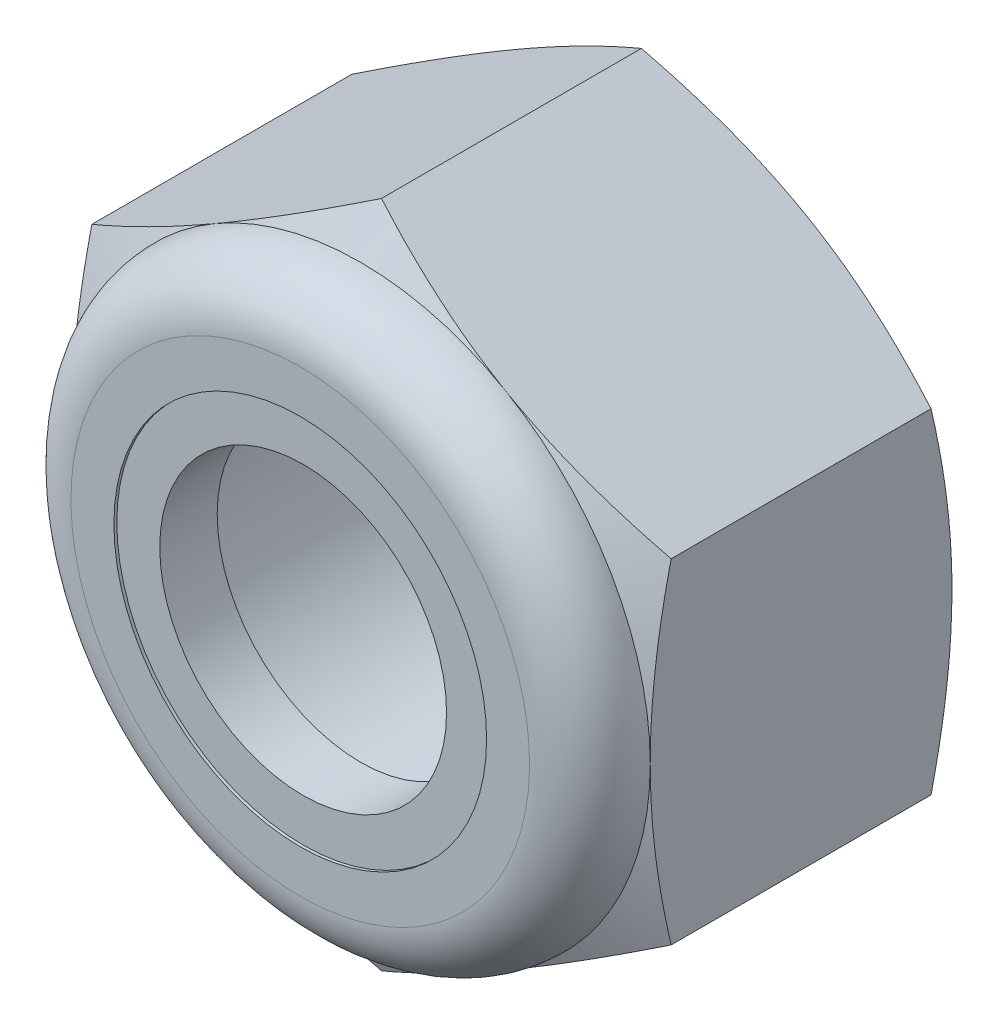
SolidWorks part; units mm, degrees
material "Alloy Steel"
ref_plane "Front Plane" through (0, 0, 0) normal (0, 0, 1) x (1, 0, 0)
ref_plane "Top Plane" through (0, 0, 0) normal (0, 1, 0) x (1, 0, 0)
ref_plane "Right Plane" through (0, 0, 0) normal (1, 0, 0) x (0, 0, -1)
sketch "Sketch1" plane through (0, 0, 0) normal (0, 0, 1) x (1, 0, 0)
  line L1 (0, 4.6188) -> (-4, 2.3094)
  line L2 (-4, 2.3094) -> (-4, -2.3094)
  line L3 (-4, -2.3094) -> (0, -4.6188)
  line L4 (0, -4.6188) -> (4, -2.3094)
  line L5 (4, -2.3094) -> (4, 2.3094)
  line L6 (4, 2.3094) -> (0, 4.6188)
  circle A0 centre (0, 0) radius 4 construction
  circle A1 centre (0, 0) radius 2.5
  point P10 (0, -2.5)
  point P11 (0, 2.5)
  point P12 (0, 4)
  dimension "Thread Size" = 5
  dimension "Width" = 8
sketch "Sketch2" plane through (0, 0, 0) normal (1, 0, 0) x (0, 0, -1)
  line L0 (2.5, 0) -> (-2.5, 0) construction
  line L1 (-2.5, 2.5) -> (2.5, 2.5) construction
  line L2 (-2.46, -2.5735) -> (-3.77, -2.5735) construction
  line L3 (-3.25, 2.5866) -> (-2.45, 2.5866) construction
  line L4 (-2.45, 2.5866) -> (-2.85, 1.8938) construction
  line L5 (-2.85, 1.8938) -> (-3.25, 2.5866) construction
  line L6 (-3.2, 2.5) -> (-2.5, 2.5) construction
  line L7 (-2.9, 1.9804) -> (-2.8, 1.9804) construction
  line L8 (-2.85, 1.9804) -> (-2.85, 1.8938) construction
  line L9 (-2.85, 2.5) -> (-2.85, 2.5866) construction
  line L10 (-2.475, 2.5433) -> (-3.225, 2.5433)
  line L11 (-3.225, 2.5433) -> (-2.9, 1.9804)
  line L12 (-2.9, 1.9804) -> (-2.8, 1.9804)
  line L13 (-2.8, 1.9804) -> (-2.475, 2.5433)
  line L14 (2.5, 0) -> (3.77, 0)
  line L15 (3.77, 0) -> (3.77, 5.8888)
  line L16 (0, 5.8888) -> (0, 4.6188) construction
  line L17 (0, 4.6188) -> (0, 2.3094) construction
  line L18 (2.5, 4) -> (-1.6667, 4) construction
  line L19 (-2.9, -1.9804) -> (-2.8, -1.9804) construction
  line L20 (2.5, 4) -> (2.5, 0)
  line L21 (2.2114, 4.6188) -> (-1.3781, 4.6188)
  line L22 (2.5, 4) -> (2.2114, 4.6188)
  line L23 (-2.5, 0) -> (-2.5, 3.1667) construction
  line L24 (-1.6667, 4) -> (-1.3781, 4.6188)
  line L25 (3.77, 5.8888) -> (-3.77, 5.8888)
  line L26 (-2.5, 3.1667) -> (-3.77, 3.1667)
  line L27 (-3.77, 3.1667) -> (-3.77, 5.8888)
  line L28 (-2.46, 3.1667) -> (-2.46, 1.9804) construction
  line L29 (-2.46, 2.5735) -> (-3.77, 2.5735)
  line L30 (-3.77, 2.5735) -> (-3.77, 0)
  line L31 (-3.77, 0) -> (-1.6667, 0)
  line L32 (-1.6667, 0) -> (-1.6667, 3.96)
  line L33 (-2.46, 2.5735) -> (-2.46, 3.1667)
  arc A0 (-1.6667, 4) -> (-2.5, 3.1667) centre (-1.6667, 3.1667) ccw
  arc A1 (-1.6667, 3.96) -> (-2.46, 3.1667) centre (-1.6667, 3.1667) ccw
  point P4 (0, 0)
  point P18 (-2.85, 2.5433)
  point P22 (-2.85, 2.5433)
  point P33 (0, 4.6188)
  point P48 (-3.77, -2.5735)
  point P51 (-2.9, -1.9804)
  dimension "Height" = 5
  dimension "Pitch" = 0.8
  dimension "D1" = 0.1
  dimension "D2" = 1.27
  dimension "D3" = 25
  dimension "D4" = 0.8333
  dimension "D5" = 25
  dimension "D6" = 0.04
sketch "Sketch3" plane through (0, 0, 0) normal (0, 0, 1) x (1, 0, 0)
  line L0 (0, -4.6188) -> (4, -2.3094) construction
  line L1 (4, -2.3094) -> (4, 2.3094) construction
  line L2 (4, 2.3094) -> (0, 4.6188) construction
  line L3 (0, 4.6188) -> (-4, 2.3094) construction
  line L4 (-4, 2.3094) -> (-4, -2.3094) construction
  line L5 (-4, -2.3094) -> (0, -4.6188) construction
  line L6 (0, -4.6188) -> (4, -2.3094)
  line L7 (4, -2.3094) -> (4, 2.3094)
  line L8 (4, 2.3094) -> (0, 4.6188)
  line L9 (0, 4.6188) -> (-4, 2.3094)
  line L10 (-4, 2.3094) -> (-4, -2.3094)
  line L11 (-4, -2.3094) -> (0, -4.6188)
  circle A0 centre (0, 0) radius 2.5 construction
  circle A1 centre (0, 0) radius 2.5
extrude "Boss-Extrude1" add sketch "Sketch3" along normal mid plane 5
sketch "Sketch4" plane through (0, 0, 0) normal (1, 0, 0) x (0, 0, -1)
  line L0 (3.77, 5.8888) -> (-3.77, 5.8888) construction
  line L1 (-3.77, 3.1667) -> (-3.77, 5.8888) construction
  line L2 (-2.5, 3.1667) -> (-3.77, 3.1667) construction
  line L3 (-1.6667, 4) -> (-1.3781, 4.6188) construction
  line L4 (2.2114, 4.6188) -> (-1.3781, 4.6188) construction
  line L5 (2.5, 4) -> (2.2114, 4.6188) construction
  line L6 (2.5, 4) -> (2.5, 0) construction
  line L7 (2.5, 0) -> (3.77, 0) construction
  line L8 (3.77, 0) -> (3.77, 5.8888) construction
  line L9 (-3.77, 2.5735) -> (-3.77, 0) construction
  line L10 (-3.77, 0) -> (-1.6667, 0) construction
  line L11 (-1.6667, 0) -> (-1.6667, 3.96) construction
  line L12 (-2.46, 2.5735) -> (-2.46, 3.1667) construction
  line L13 (-2.46, 2.5735) -> (-3.77, 2.5735) construction
  line L14 (3.77, 5.8888) -> (-3.77, 5.8888)
  line L15 (-3.77, 3.1667) -> (-3.77, 5.8888)
  line L16 (-2.5, 3.1667) -> (-3.77, 3.1667)
  line L17 (-1.6667, 4) -> (-1.3781, 4.6188)
  line L18 (2.2114, 4.6188) -> (-1.3781, 4.6188)
  line L19 (2.5, 4) -> (2.2114, 4.6188)
  line L20 (2.5, 4) -> (2.5, 0)
  line L21 (2.5, 0) -> (3.77, 0)
  line L22 (3.77, 0) -> (3.77, 5.8888)
  line L23 (-3.77, 2.5735) -> (-3.77, 0)
  line L24 (-3.77, 0) -> (-1.6667, 0)
  line L25 (-1.6667, 0) -> (-1.6667, 3.96)
  line L26 (-2.46, 2.5735) -> (-2.46, 3.1667)
  line L27 (-2.46, 2.5735) -> (-3.77, 2.5735)
  arc A0 (-1.6667, 4) -> (-2.5, 3.1667) centre (-1.6667, 3.1667) ccw construction
  arc A1 (-1.6667, 3.96) -> (-2.46, 3.1667) centre (-1.6667, 3.1667) ccw construction
  arc A2 (-1.6667, 4) -> (-2.5, 3.1667) centre (-1.6667, 3.1667) ccw
  arc A3 (-1.6667, 3.96) -> (-2.46, 3.1667) centre (-1.6667, 3.1667) ccw
revolve "Cut-Revolve1" cut sketch "Sketch4" angle 360 about L0
sketch "Sketch5" plane through (0, 0, 0) normal (1, 0, 0) x (0, 0, -1)
  line L0 (-2.46, 3.1667) -> (-2.46, 1.9804) construction
  line L1 (-1.6667, 0) -> (-1.6667, 3.96) construction
  line L2 (-2.46, 3.1667) -> (-2.46, 1.9804)
  line L3 (-1.6667, 1.9804) -> (-1.6667, 3.96)
  line L4 (-2.46, 1.9804) -> (-1.6667, 1.9804)
  arc A0 (-1.6667, 3.96) -> (-2.46, 3.1667) centre (-1.6667, 3.1667) ccw construction
  arc A1 (-1.6667, 3.96) -> (-2.46, 3.1667) centre (-1.6667, 3.1667) ccw
revolve "Revolve1" add sketch "Sketch5" angle 360 about L0
sketch "Sketch6" [suppressed] plane through (0, 0, 2.5) normal (0, 0, 1) x (1, 0, 0)
  circle A0 centre (0, 0) radius 2.5 construction
  circle A1 centre (0, 0) radius 2.5
curve "Helix/Spiral1" [suppressed] pitch 0.8 height 5.8 turns 7.25
sketch "Sketch7" [suppressed] plane through (0, 0, 0) normal (1, 0, 0) x (0, 0, -1)
  line L0 (-3.225, 2.5433) -> (-2.9, 1.9804) construction
  line L1 (-2.9, 1.9804) -> (-2.8, 1.9804) construction
  line L2 (-2.8, 1.9804) -> (-2.475, 2.5433) construction
  line L3 (-2.475, 2.5433) -> (-3.225, 2.5433) construction
  line L4 (-3.225, 2.5433) -> (-2.9, 1.9804)
  line L5 (-2.9, 1.9804) -> (-2.8, 1.9804)
  line L6 (-2.8, 1.9804) -> (-2.475, 2.5433)
  line L7 (-2.475, 2.5433) -> (-3.225, 2.5433)
sweep "Sweep1" [suppressed] add profiles "Sketch7" path "Helix/Spiral1"
sketch "Sketch8" [suppressed] plane through (0, 0, -2.5) normal (0, 0, -1) x (-1, 0, 0)
  circle A2 centre (0, 0) radius 2.5433
  point P2 (0, 2.5433)
extrude "Cut-Extrude1" [suppressed] cut sketch "Sketch8" along normal through all and the other way through all draft 60
sketch "Sketch9" [suppressed] plane through (0, 0, 1.6667) normal (0, 0, 1) x (1, 0, 0)
  circle A2 centre (0, 0) radius 2.5433
  circle A3 centre (0, 0) radius 1.9804 construction
  point P2 (0, 2.5433)
  point P4 (0, 1.9804)
extrude "Cut-Extrude2" [suppressed] cut sketch "Sketch9" along normal through all and the other way through all draft 60
equation "\"D1@Sketch2\" = \"Pitch@Sketch2\" / 8"
equation "\"D4@Sketch2\"=\"Height@Sketch2\"/6"
equation "\"D1@Boss-Extrude1\"=\"Height@Sketch2\""
equation "\"D3@Helix/Spiral1\"=\"Height@Sketch2\"+\"Pitch@Sketch2\""
equation "\"D4@Helix/Spiral1\"=\"Pitch@Sketch2\""
equation "\"D6@Sketch2\"=\"Pitch@Sketch2\"*0.05"
